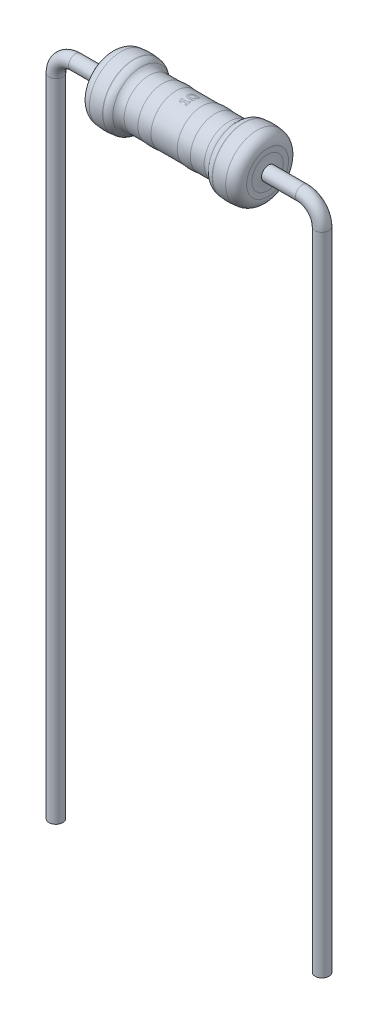
SolidWorks part; units mm, degrees
material "Plain Carbon Steel"
ref_plane "Front Plane" through (0, 0, 0) normal (0, 0, 1) x (1, 0, 0)
ref_plane "Top Plane" through (0, 0, 0) normal (0, 1, 0) x (1, 0, 0)
ref_plane "Right Plane" through (0, 0, 0) normal (1, 0, 0) x (0, 0, -1)
sketch "Sketch1" plane through (0, 0, 0) normal (0, 0, 1) x (1, 0, 0)
  line L0 (-4.33, 0) -> (4.33, 0)
  line L1 (-5.08, -0.75) -> (-5.08, -25.4)
  line L2 (5.08, -0.75) -> (5.08, -25.4)
  line L3 (-5.08, -25.4) -> (5.08, -25.4) construction
  line L4 (0, 0) -> (0, -25.4) construction
  arc A0 (-4.33, 0) -> (-5.08, -0.75) centre (-4.33, -0.75) ccw
  arc A1 (4.33, 0) -> (5.08, -0.75) centre (4.33, -0.75) cw
  dimension "D2" = 0.75
  dimension "D1" = 10.16
  dimension "D3" = 25.4
ref_plane "Plane1" through (-5.08, -25.4, 0) normal (0, -1, 0) x (-1, 0, 0)
sketch "Sketch2" plane through (-5.08, -25.4, 0) normal (0, -1, 0) x (-1, 0, 0)
  circle A0 centre (0, 0) radius 0.265
  dimension "D1" = 0.53
sweep "Sweep1" add profiles "Sketch2" path "Sketch1"
sketch "Sketch3" plane through (0, 0, 0) normal (0, 0, 1) x (1, 0, 0)
  line L0 (-3, 0) -> (3, 0)
  line L5 (-3, 0) -> (-3, 1.2)
  line L6 (3, 0) -> (3, 1.2)
  line L7 (-3, 1.2) -> (-1.75, 1.2)
  line L8 (3, 1.2) -> (1.75, 1.2)
  line L9 (-1.75, 1.2) -> (-1.75, 0.95)
  line L10 (-1.75, 0.95) -> (1.75, 0.95)
  line L11 (1.75, 0.95) -> (1.75, 1.2)
  line L12 (0, 0) -> (0, 0.95) construction
  dimension "D1" = 6
  dimension "D2" = 1.2
  dimension "D3" = 3.5
  dimension "D4" = 0.95
  dimension "D5" = 0.25
revolve "Revolve1" add sketch "Sketch3" angle 360 about L0
fillet "Fillet-1" radius 0.35 2 edges at (1.75, 0, 1.2) (-1.75, 0, 1.2)
fillet "Fillet-2" radius 0.4 4 edges at (3, 0, 1.2) (-3, 0, 1.2) (1.75, 0, 0.95) (-1.75, 0, 0.95)
sketch "Sketch5" plane through (0, 0, 0) normal (0, 0, 1) x (1, 0, 0)
  line L16 (-3, 0) -> (3, 0) construction
  line L17 (-2.6, 1.2) -> (-2.1, 1.2) construction
  line L18 (-2.6, 1.2) -> (-2.6, 0)
  line L19 (-2.6, 0) -> (-2.1, 0)
  line L20 (-2.1, 1.2) -> (-2.1, 0)
  line L21 (-1.75, 0.95) -> (1.75, 0.95) construction
  line L22 (2.6, 1.2) -> (2.1, 1.2) construction
  line L23 (2.6, 1.2) -> (2.6, 0)
  line L24 (2.6, 0) -> (2.1, 0)
  line L25 (2.1, 1.2) -> (2.1, 0)
  line L26 (-0.5, 0.95) -> (-1, 0.95) construction
  line L27 (-0.5, 0.95) -> (-0.5, 0)
  line L28 (-0.5, 0) -> (-1, 0)
  line L29 (-1, 0.95) -> (-1, 0)
  line L30 (-2.35, 1.2) -> (-2.35, 1.22) construction
  line L31 (1, 0.95) -> (0.5, 0.95) construction
  line L32 (1, 0.95) -> (1, 0)
  line L33 (1, 0) -> (0.5, 0)
  line L34 (0.5, 0.95) -> (0.5, 0)
  line L35 (-0.75, 0.95) -> (-0.75, 0.97) construction
  line L36 (0.75, 0.95) -> (0.75, 0.97) construction
  line L37 (2.35, 1.2) -> (2.35, 1.22) construction
  line L48 (-3, 0) -> (-3, 0.6)
  line L49 (-3, 0) -> (-3, 1.2) construction
  line L50 (-3, 0) -> (-3.05, 0)
  line L51 (-3.05, 0) -> (-3.05, 0.2)
  line L52 (3, 0) -> (3.05, 0)
  line L53 (3.05, 0) -> (3.05, 0.2)
  line L54 (3, 0) -> (3, 0.6)
  line L55 (3, 0) -> (3, 1.2) construction
  arc A0 (-2.6, 1.2) -> (-2.1, 1.2) centre (-2.35, -0.3525) cw
  arc A1 (-1, 0.95) -> (-0.5, 0.95) centre (-0.75, -0.6025) cw
  arc A2 (0.5, 0.95) -> (1, 0.95) centre (0.75, -0.6025) cw
  arc A3 (2.1, 1.2) -> (2.6, 1.2) centre (2.35, -0.3525) cw
  arc A6 (-3, 0.6) -> (-3.05, 0.2) centre (-4.625, 0.6) cw
  arc A7 (3.05, 0.2) -> (3, 0.6) centre (4.625, 0.6) cw
  dimension "D4" = 0.02
  dimension "D5" = 0.05
  dimension "D7" = 0.6
  dimension "D1" = 0.5
  dimension "D2" = 0.5
  dimension "D3" = 0.5
  dimension "D6" = 0.2
revolve "Revolve3" add sketch "Sketch5" angle 360 about L19
ref_plane "Plane2" through (0, 2, 0) normal (0, 1, 0) x (1, 0, 0)
sketch "Sketch6" plane through (0, 2, 0) normal (0, 1, 0) x (1, 0, 0)
  line L0 (0, 0) -> (0.15, 0) construction
  line L1 (0.15, 0.95) -> (0.15, -0.95) construction
  line L2 (0.5, 0.95) -> (-0.5, 0.95) construction
  text T0 "1Ω" font "Calibri" height 0.3
  dimension "D1" = 0.15
wrap "Wrap1" sketch "Sketch6" wrap type scribe source sketch "Sketch6" face at (-0.5, -0.95, 0)
